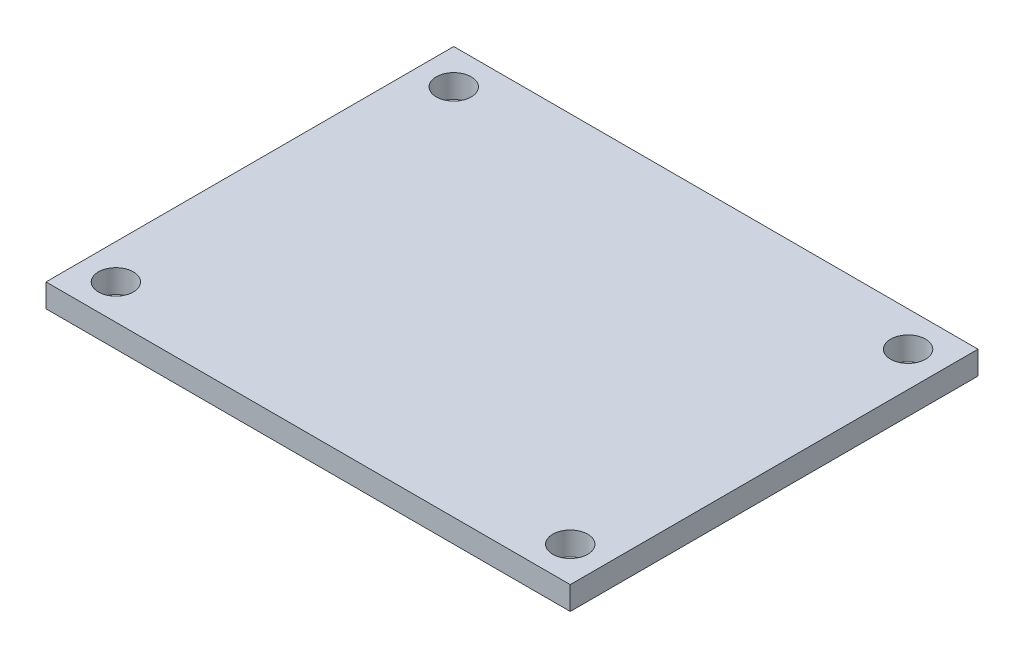
SolidWorks part; units mm, degrees
ref_plane "Front Plane" through (0, 0, 0) normal (0, 0, 1) x (1, 0, 0)
ref_plane "Top Plane" through (0, 0, 0) normal (0, 1, 0) x (1, 0, 0)
ref_plane "Right Plane" through (0, 0, 0) normal (1, 0, 0) x (0, 0, -1)
sketch "Sketch1" plane through (0, 0, 0) normal (0, 1, 0) x (1, 0, 0)
  line L0 (0, 0) -> (-13.7039, 0) construction
  line L1 (-22.5, -17.5) -> (22.5, -17.5)
  line L2 (-22.5, -17.5) -> (-22.5, 17.5)
  line L3 (-22.5, 17.5) -> (22.5, 17.5)
  line L4 (22.5, -17.5) -> (22.5, 17.5)
  line L5 (-22.5, -17.5) -> (22.5, 17.5) construction
  line L6 (-22.5, 17.5) -> (22.5, -17.5) construction
  line L7 (0, 0) -> (0, 10.9277) construction
  circle A0 centre (-19.5, 14.5) radius 1.5
  circle A1 centre (19.5, 14.5) radius 1.5
  circle A2 centre (-19.5, -14.5) radius 1.5
  circle A3 centre (19.5, -14.5) radius 1.5
  point P0 (0, 0)
  point P13 (-19.7076, 13.3763)
  point P14 (-22.5, 13.2801)
  dimension "D5" = 3
  dimension "D1" = 45
  dimension "D2" = 35
  dimension "D3" = 3
  dimension "D4" = 3
extrude "Boss-Extrude1" add sketch "Sketch1" along normal blind 2
